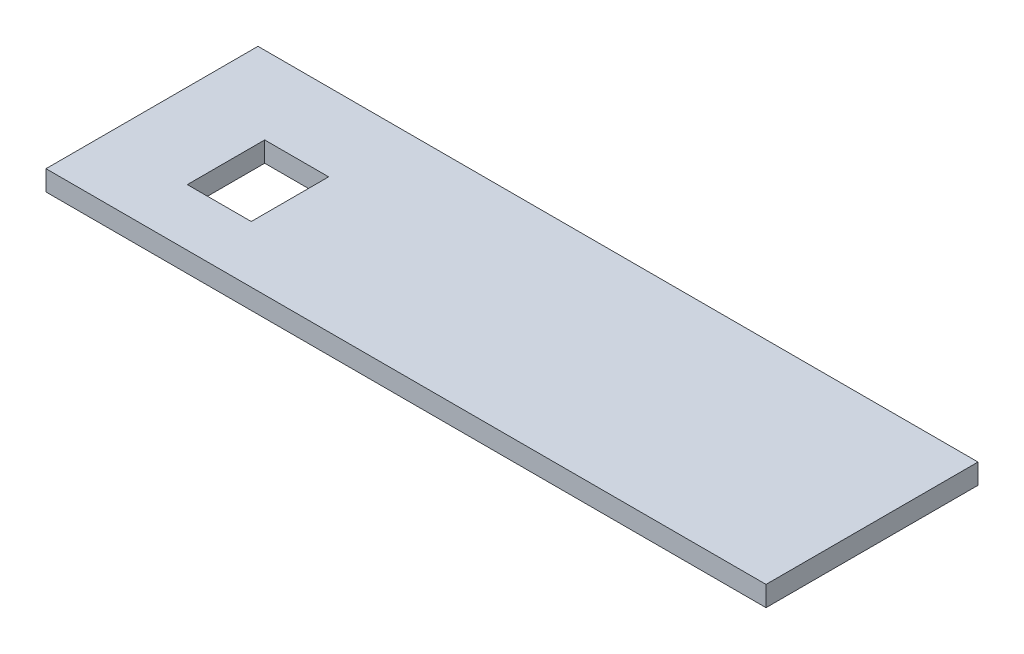
SolidWorks part; units mm, degrees
ref_plane "Спереди" through (0, 0, 0) normal (0, 0, 1) x (1, 0, 0)
ref_plane "Сверху" through (0, 0, 0) normal (0, 1, 0) x (1, 0, 0)
ref_plane "Справа" through (0, 0, 0) normal (1, 0, 0) x (0, 0, -1)
other "Configuration Table"
sketch "Эскиз1" plane through (0, 0, 0) normal (0, 1, 0) x (1, 0, 0)
  line L1 (0, -31.5) -> (107, -31.5)
  line L2 (0, -31.5) -> (0, 0)
  line L3 (0, 0) -> (107, 0)
  line L4 (107, -31.5) -> (107, 0)
  line L5 (12.55, -23.05) -> (22.05, -23.05)
  line L6 (12.55, -23.05) -> (12.55, -11.55)
  line L7 (12.55, -11.55) -> (22.05, -11.55)
  line L8 (22.05, -23.05) -> (22.05, -11.55)
extrude "Бобышка-Вытянуть1" add sketch "Эскиз1" along normal blind 3
